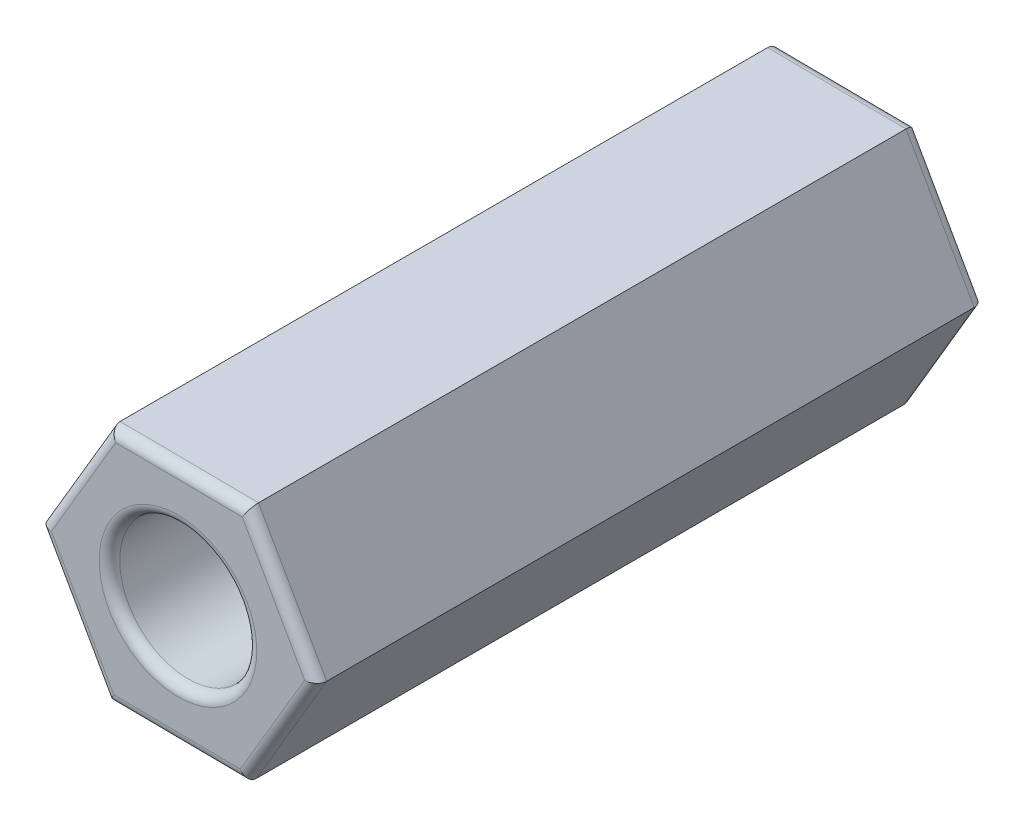
SolidWorks part; units mm, degrees
ref_plane "Спереди" through (0, 0, 0) normal (0, 0, 1) x (1, 0, 0)
ref_plane "Сверху" through (0, 0, 0) normal (0, 1, 0) x (1, 0, 0)
ref_plane "Справа" through (0, 0, 0) normal (1, 0, 0) x (0, 0, -1)
sketch "Эскиз1" plane through (0, 0, 0) normal (0, 0, 1) x (1, 0, 0)
  line L1 (2.0523, 3.4816) -> (-1.989, 3.5181)
  line L2 (-1.989, 3.5181) -> (-4.0413, 0.0366)
  line L3 (-4.0413, 0.0366) -> (-2.0523, -3.4816)
  line L4 (-2.0523, -3.4816) -> (1.989, -3.5181)
  line L5 (1.989, -3.5181) -> (4.0413, -0.0366)
  line L6 (4.0413, -0.0366) -> (2.0523, 3.4816)
  circle A0 centre (0, 0) radius 3.5 construction
  dimension "D1" = 7
extrude "Бобышка-Вытянуть1" add sketch "Эскиз1" along normal blind 19.5
sketch "Эскиз2" plane through (0, 0, 19.5) normal (0, 0, 1) x (1, 0, 0)
  line L0 (-1.3229, 1.5) -> (1.3229, 1.5)
  arc A0 (-1.3229, 1.5) -> (1.3229, 1.5) centre (0, 0) ccw
  dimension "D1" = 1.5
  dimension "D2" = 2
extrude "Вырез-Вытянуть1" cut sketch "Эскиз2" against normal blind 12.5
sketch "Эскиз3" plane through (0, 0, 19.5) normal (0, 0, 1) x (1, 0, 0)
  circle A0 centre (0, 0) radius 2
extrude "Вырез-Вытянуть2" cut sketch "Эскиз3" against normal blind 4
fillet "Скругление1" radius 0.3 13 edges at (0.0317, 3.4999, 0) (-3.0151, 1.7773, 0) (-3.0468, -1.7225, 0) (-0.0317, -3.4999, 0) (3.0151, -1.7773, 0) (3.0468, 1.7225, 0) (3.0151, -1.7773, 19.5) (-0.0317, -3.4999, 19.5) (-3.0468, -1.7225, 19.5) (-3.0151, 1.7773, 19.5) (0.0317, 3.4999, 19.5) (3.0468, 1.7225, 19.5) (2, 0, 19.5)
fillet "Скругление2" radius 0.2 1 edges at (0, 1.5, 15.5)
